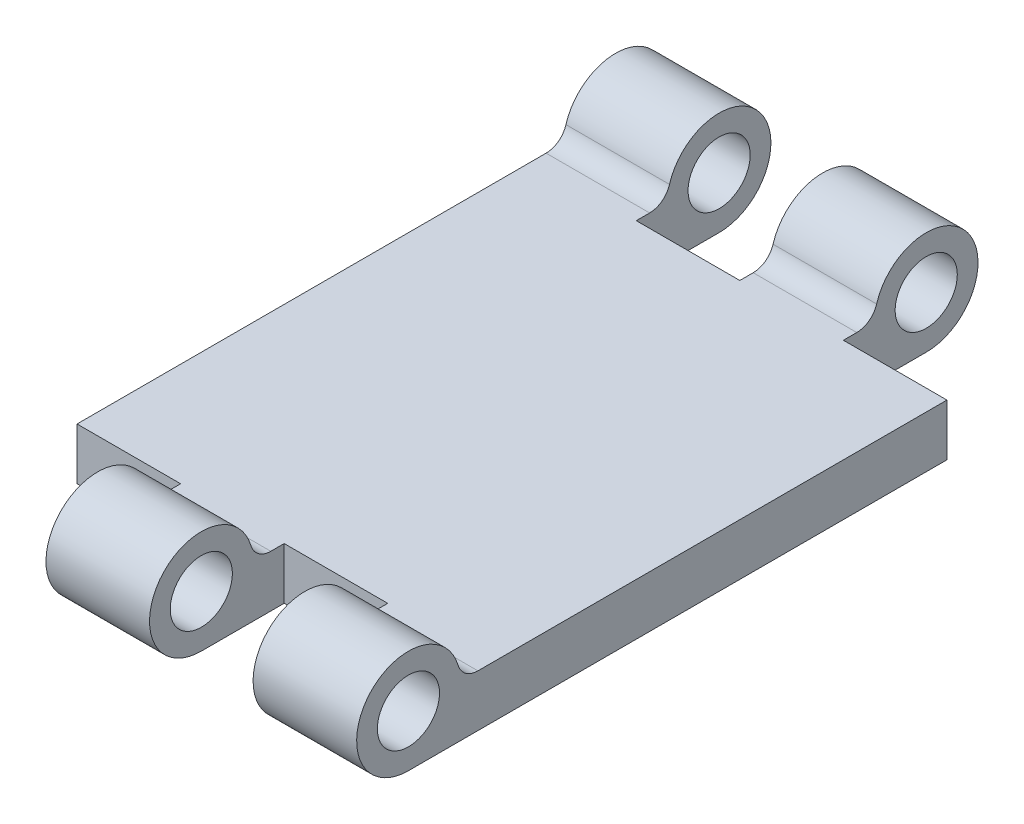
SolidWorks part; units mm, degrees
ref_plane "Front Plane" through (0, 0, 0) normal (0, 0, 1) x (1, 0, 0)
ref_plane "Top Plane" through (0, 0, 0) normal (0, 1, 0) x (1, 0, 0)
ref_plane "Right Plane" through (0, 0, 0) normal (1, 0, 0) x (0, 0, -1)
sketch "Sketch1" plane through (0, 0, 0) normal (1, 0, 0) x (0, 0, -1)
  line L0 (-125, 0) -> (-1375, 0)
  line L3 (-1500, -125) -> (0, -125)
  circle A0 centre (0, 0) radius 75
  circle A1 centre (0, 0) radius 125
  circle A2 centre (-1500, 0) radius 75
  circle A3 centre (-1500, 0) radius 125
  dimension "D1" = 150
  dimension "D2" = 250
  dimension "D3" = 1500
extrude "Boss-Extrude1" add sketch "Sketch1" along normal mid plane 1000 contours A3 L3 A1 L0 region at (0, -63.9231, 750)
extrude "Boss-Extrude2" add sketch "Sketch1<3>" along normal blind 250 contours A1 A0 region at (0, 121.4645, 0)
sketch "Sketch1<3>" plane through (0, 0, 0) normal (1, 0, 0) x (0, 0, -1) same geometry as "Sketch1"
extrude "Boss-Extrude3" add sketch "Sketch1<4>" against normal blind 250 contours A3 A2 region at (0, -85.8883, 1414.1117)
sketch "Sketch1<4>" plane through (0, 0, 0) normal (1, 0, 0) x (0, 0, -1) same geometry as "Sketch1"
extrude "Boss-Extrude4" add sketch "Sketch1<5>" against normal blind 250 from offset 250 contours A1 A0 region at (0, 121.4645, 0) offset against normal yes
sketch "Sketch1<5>" plane through (0, 0, 0) normal (1, 0, 0) x (0, 0, -1) same geometry as "Sketch1"
extrude "Boss-Extrude5" add sketch "Sketch1<6>" along normal blind 250 from offset 250 contours A3 A2 region at (0, -85.8883, 1414.1117)
sketch "Sketch1<6>" plane through (0, 0, 0) normal (1, 0, 0) x (0, 0, -1) same geometry as "Sketch1"
sketch "Sketch2" plane through (0, 0, 0) normal (0, 1, 0) x (1, 0, 0)
  line L0 (-250, 550.6824) -> (-250, -200)
  line L1 (-250, -200) -> (0, -200)
  line L2 (0, -200) -> (0, 342.9707)
  line L3 (-250, -125) -> (-250, 125) construction
  line L5 (0, 342.9707) -> (250, 342.9707)
  line L6 (250, 342.9707) -> (250, -200)
  line L7 (250, -200) -> (760.2143, -200)
  line L8 (250, -125) -> (250, 125) construction
  line L9 (-250, 550.6824) -> (760.2143, 550.6824)
  line L10 (760.2143, 550.6824) -> (760.2143, -200)
  line L11 (250, -2214.6305) -> (250, -1300)
  line L12 (250, -1300) -> (0, -1300)
  line L13 (0, -1300) -> (0, -1946.0531)
  line L14 (0, -1946.0531) -> (-250, -1946.0531)
  line L15 (-250, -1946.0531) -> (-250, -1300)
  line L16 (-250, -1300) -> (-708.696, -1300)
  line L17 (-708.696, -1300) -> (-708.696, -2214.6305)
  line L18 (-708.696, -2214.6305) -> (250, -2214.6305)
  line L19 (-250, -1375) -> (-250, -1625) construction
  line L20 (-250, -1500) -> (-500, -1500) construction
  dimension "D1" = 200
  dimension "D2" = 200
extrude "Cut-Extrude1" cut sketch "Sketch2" against normal blind 250 and the other way blind 250
fillet "Fillet1" radius 50 4 edges at (-125, 0, 1375) (375, 0, 1375) (125, 0, 125) (-375, 0, 125)
